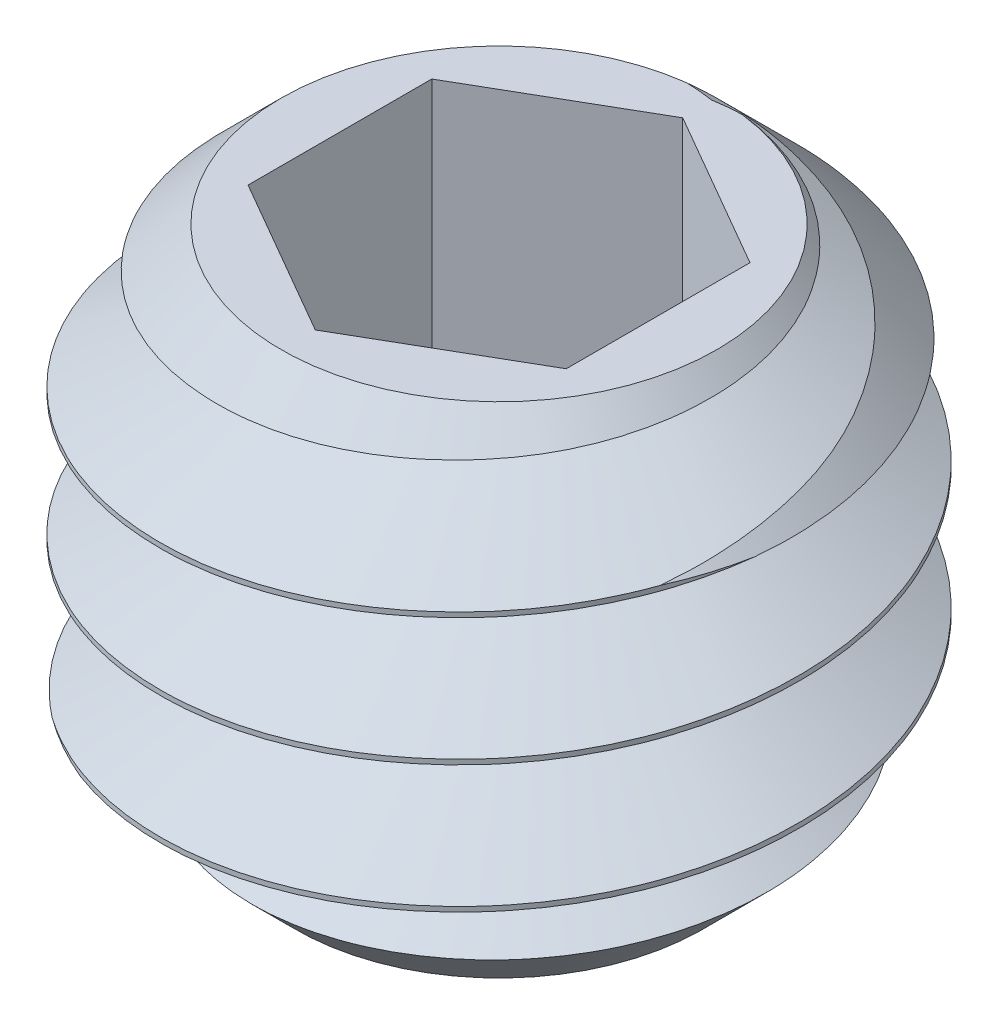
SolidWorks part; units mm, degrees
ref_plane "Front Plane" through (0, 0, 0) normal (0, 0, 1) x (1, 0, 0)
ref_plane "Top Plane" through (0, 0, 0) normal (0, 1, 0) x (1, 0, 0)
ref_plane "Right Plane" through (0, 0, 0) normal (1, 0, 0) x (0, 0, -1)
sketch "Sketch1" plane through (0, 0, 0) normal (0, 0, 1) x (1, 0, 0)
  line L0 (0, 0) -> (0, 54.6222) construction
  line L1 (0, 0.5866) -> (-1.016, 0)
  line L2 (-1.016, 0) -> (-1.27, 0)
  line L3 (-1.27, 0) -> (-1.9939, 0.7239)
  line L4 (-1.9939, 0.7239) -> (-1.9939, 2.54)
  line L5 (-1.9939, 2.54) -> (-1.3589, 3.175)
  line L6 (-1.3589, 3.175) -> (0, 3.175)
  line L7 (0, 3.175) -> (0, 0.5866)
  dimension "D1" = 60
  dimension "D2" = 2.032
  dimension "D3" = 135
  dimension "D4" = 135
  dimension "D5" = 0.635
  dimension "D6" = 3.9878
  dimension "D7" = 0.254
  dimension "D8" = 3.175
revolve "Revolve1" add sketch "Sketch1" angle 360 about L0
sketch "Sketch2" plane through (0, 3.175, 0) normal (0, 1, 0) x (1, 0, 0)
  line L0 (0, 0) -> (0, 1.3178) construction
  line L1 (0, 1.1457) -> (-0.9922, 0.5728)
  line L2 (-0.9922, 0.5728) -> (-0.9922, -0.5728)
  line L3 (-0.9922, -0.5728) -> (0, -1.1457)
  line L4 (0, -1.1457) -> (0.9922, -0.5728)
  line L5 (0.9922, -0.5728) -> (0.9922, 0.5728)
  line L6 (0.9922, 0.5728) -> (0, 1.1457)
  circle A0 centre (0, 0) radius 0.9922 construction
  dimension "D1" = 1.9844
extrude "Cut-Extrude1" cut sketch "Sketch2" against normal blind 1.778
sketch "Sketch3" plane through (0, 3.175, 0) normal (0, 1, 0) x (1, 0, 0)
  circle A0 centre (0, 0) radius 1.9939 construction
  circle A1 centre (0, 0) radius 1.9939
curve "Helix/Spiral1" pitch 0.795 height 9.525 radius 1.9939 centre (0, 3.175, 0) axis (0, -1, 0) start towards (0, 0, 1)
sketch "Sketch4" plane through (0, 0, 0) normal (1, 0, 0) x (0, 0, -1)
  line L0 (-2.0193, 3.9687) -> (-2.0193, 3.175)
  line L1 (-2.0193, 3.175) -> (-1.3319, 3.5719)
  line L2 (-1.3319, 3.5719) -> (-2.0193, 3.9687)
  line L3 (-1.3319, 3.5719) -> (-2.0193, 3.5719) construction
  line L5 (-2.0193, 3.9687) -> (-1.3319, 4.3656) construction
  line L6 (-1.3319, 4.3656) -> (-2.0193, 4.7625) construction
  line L7 (-2.0193, 4.7625) -> (-2.0193, 3.9687) construction
  line L8 (1.3589, 3.175) -> (-1.3589, 3.175) construction
  line L10 (0, 3.175) -> (0, 10.7636) construction
  dimension "D1" = 60
  dimension "D2" = 0.7937
  dimension "D3" = 4.0386
sweep "Cut-Sweep3" cut profiles "Sketch4" path "Helix/Spiral1" align with end faces yes
